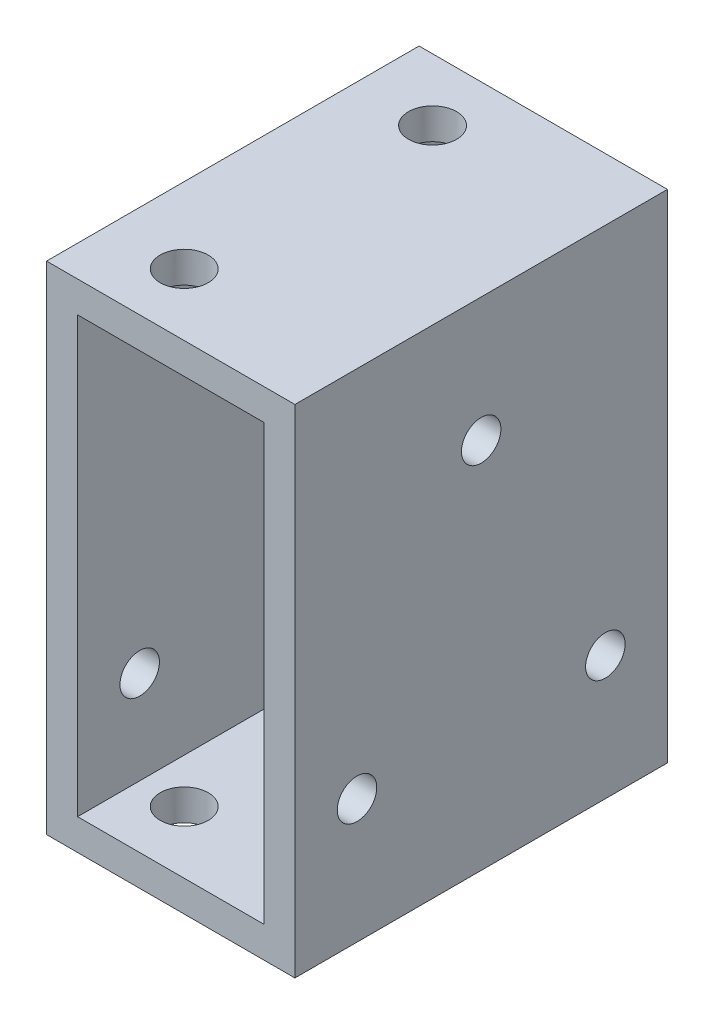
SolidWorks part; units mm, degrees
ref_plane "Front Plane" through (0, 0, 0) normal (0, 0, 1) x (1, 0, 0)
ref_plane "Top Plane" through (0, 0, 0) normal (0, 1, 0) x (1, 0, 0)
ref_plane "Right Plane" through (0, 0, 0) normal (1, 0, 0) x (0, 0, -1)
sketch "Sketch1" plane through (0, 0, 0) normal (0, 0, 1) x (1, 0, 0)
  line L0 (-9.525, 22.225) -> (9.525, 22.225)
  line L1 (-12.7, 25.4) -> (12.7, 25.4)
  line L2 (-12.7, 25.4) -> (-12.7, -25.4)
  line L3 (-12.7, -25.4) -> (12.7, -25.4)
  line L4 (12.7, 25.4) -> (12.7, -25.4)
  line L5 (-12.7, 25.4) -> (12.7, -25.4) construction
  line L6 (-12.7, -25.4) -> (12.7, 25.4) construction
  line L7 (9.525, 22.225) -> (9.525, -22.225)
  line L8 (-9.525, -22.225) -> (9.525, -22.225)
  line L9 (-9.525, 22.225) -> (-9.525, -22.225)
  point P0 (0, 0)
  dimension "D1" = 25.4
  dimension "D2" = 50.8
  dimension "D3" = 3.175
extrude "Boss-Extrude1" add sketch "Sketch1" along normal mid plane 38.1
hole_wizard "#10 (0.1935) Diameter Hole1" positions "Sketch3" profile "Sketch2" hole size "#10" standard "ANSI Inch" end condition through all
sketch "Sketch3" plane through (0, 25.4, 0) normal (0, 1, 0) x (1, 0, 0)
  line L0 (12.7, -19.05) -> (-12.7, -19.05) construction
  line L1 (-4.9712, 12.7) -> (-4.9712, -12.7) construction
  point P0 (-4.9712, -12.7)
  point P2 (-4.9712, 12.7)
  dimension "D1" = 25.4
  dimension "D2" = 6.35
sketch "Sketch2" plane through (-4.9712, 25.4, 12.7) normal (1, 0, 0) x (0, 0, 1)
  line L0 (0, 0) -> (0, 50.8)
  line L1 (0, 50.8) -> (2.4574, 50.8)
  line L2 (2.4574, 50.8) -> (2.4574, 0)
  line L5 (2.4574, 0) -> (0, 0)
  line L11 (0, -6.35) -> (0, 107.95) construction
  dimension "Thru Hole Dia." = 4.9149
  dimension "Thru Hole Depth" = 50.8
hole_wizard "#10-32 Tapped Hole1" positions "Sketch5" profile "Sketch4" tap size "#10-32" standard "ANSI Inch" end condition through all
sketch "Sketch5" plane through (-12.7, 0, 0) normal (-1, 0, 0) x (0, 0, 1)
  line L0 (-19.05, 25.4) -> (-19.05, -25.4) construction
  line L1 (-12.7, -12.7) -> (12.7, -12.7) construction
  line L3 (19.05, 25.4) -> (-19.05, 25.4) construction
  line L4 (19.05, -25.4) -> (-19.05, -25.4) construction
  point P0 (-12.7, -12.7)
  point P2 (12.7, -12.7)
  point P4 (0, 12.7)
  dimension "D1" = 19.05
  dimension "D2" = 6.35
  dimension "D3" = 25.4
  dimension "D4" = 12.7
  dimension "D5" = 12.7
sketch "Sketch4" plane through (-12.7, -12.7, -12.7) normal (0, 1, 0) x (0, 0, 1)
  line L0 (0, 0) -> (0, 25.4)
  line L1 (0, 25.4) -> (2.0193, 25.4)
  line L2 (2.0193, 25.4) -> (2.0193, 0)
  line L5 (2.0193, 0) -> (0, 0)
  line L11 (0, -6.35) -> (0, 107.95) construction
  dimension "Thread Major Dia." = 4.0386
  dimension "Thru Tap Drill Depth" = 25.4
